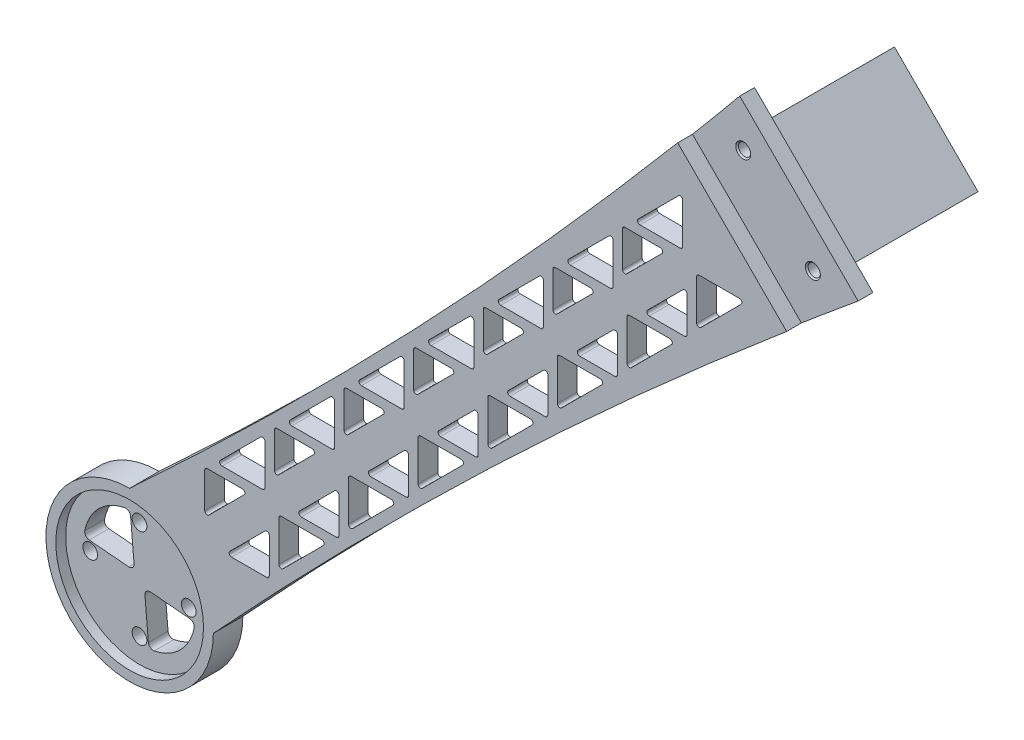
SolidWorks part; units mm, degrees
ref_plane "Front Plane" through (0, 0, 0) normal (0, 0, 1) x (1, 0, 0)
ref_plane "Top Plane" through (0, 0, 0) normal (0, 1, 0) x (1, 0, 0)
ref_plane "Right Plane" through (0, 0, 0) normal (1, 0, 0) x (0, 0, -1)
sketch "Sketch1" plane through (0, 0, 0) normal (0, 0, 1) x (1, 0, 0)
  line L0 (-180.9361, -180.9361) -> (-48, -48) construction
  line L9 (-60.0208, -35.9792) -> (-35.9792, -60.0208)
  arc A0 (-180.9361, -163.9361) -> (-163.9361, -180.9361) centre (-180.9361, -180.9361) ccw
  arc A1 (-180.9361, -163.9361) -> (-60.0208, -35.9792) centre (-1063.1797, 790.8656) ccw
  arc A2 (-163.9361, -180.9361) -> (-35.9792, -60.0208) centre (790.8656, -1063.1797) cw
  point P0 (0, 0)
  point P6 (0, 0)
  point P13 (-48, -48)
  dimension "D5" = 34
  dimension "D6" = 34
  dimension "D7" = 1300
  dimension "D1" = 48
  dimension "D2" = 188
  dimension "D3" = 48
extrude "Boss-Extrude1" add sketch "Sketch1" along normal blind 6
sketch "Sketch2" plane through (0, 0, 0) normal (0, 0, -1) x (-1, 0, 0)
  line L0 (48, -48) -> (192.9569, -192.9569) construction
  line L1 (35.9792, -60.0208) -> (60.0208, -35.9792) construction
  arc A0 (163.9361, -180.9361) -> (180.9361, -163.9361) centre (180.9361, -180.9361) ccw construction
ref_plane "Plane1" through (0, 0, 0) normal (-0.7071, 0.7071, 0) x (-0.7071, -0.7071, 0)
sketch "Sketch3" plane through (0, 0, 0) normal (-0.7071, 0.7071, 0) x (-0.7071, -0.7071, 0)
  line L0 (266.8823, 0) -> (252.3234, -40)
  line L1 (252.3234, -40) -> (240.3234, -40)
  line L2 (240.3234, -40) -> (240.3234, 0)
  line L3 (240.3234, 0) -> (266.8823, 0)
  line L5 (67.8823, 0) -> (272.8823, 0) construction
  dimension "D1" = 40
  dimension "6" = 6
  dimension "D2" = 12
  dimension "D3" = 70
extrude "Boss-Extrude2" add sketch "Sketch3" along normal blind 3 and the other way blind 3
fillet "Fillet1" radius 2 2 edges at (-178.4196, -178.4196, -40) (-169.9343, -169.9343, -40)
sketch "Sketch4" plane through (0, 0, 6) normal (0, 0, 1) x (1, 0, 0)
  line L0 (-60.0208, -35.9792) -> (-35.9792, -60.0208)
  line L1 (-35.9792, -60.0208) -> (-60.0208, -35.9792) construction
  line L2 (-35.9792, -60.0208) -> (-47.4989, -69.628)
  line L3 (-47.4989, -69.628) -> (-69.628, -47.4989)
  line L4 (-69.628, -47.4989) -> (-60.0208, -35.9792)
  arc A0 (-180.9361, -163.9361) -> (-60.0208, -35.9792) centre (-1063.1797, 790.8656) ccw construction
  arc A1 (-35.9792, -60.0208) -> (-163.9361, -180.9361) centre (790.8656, -1063.1797) ccw construction
  dimension "D1" = 15
extrude "Cut-Extrude1" cut sketch "Sketch4" against normal blind 3
sketch "Sketch9" plane through (0, 0, 3) normal (0, 0, 1) x (1, 0, 0)
  line L0 (-48, -48) -> (-56.4853, -56.4853) construction
  line L1 (-48, -48) -> (-192.9569, -192.9569) construction
  line L2 (-59.4701, -45.0152) -> (-45.0152, -59.4701) construction
  line L4 (-35.9792, -60.0208) -> (-60.0208, -35.9792) construction
  point P7 (-52.2426, -52.2426)
  point P10 (-59.3137, -45.1716)
  point P11 (-45.1716, -59.3137)
  point P14 (-52.2426, -52.2426)
  dimension "D1" = 6
  dimension "D2" = 10
  dimension "D3" = 10
sketch "Sketch5" plane through (0, 0, 0) normal (0, 0, -1) x (-1, 0, 0)
  line L0 (48, -48) -> (169.9343, -169.9343) construction
  line L1 (167.813, -172.0557) -> (172.0557, -167.813) construction
  line L2 (41.636, -58.6066) -> (58.6066, -41.636)
  line L3 (41.636, -58.6066) -> (45.8787, -62.8492)
  line L4 (58.6066, -41.636) -> (62.8492, -45.8787)
  line L5 (45.8787, -62.8492) -> (62.8492, -45.8787)
  line L6 (41.636, -58.6066) -> (62.8492, -45.8787) construction
  line L7 (58.6066, -41.636) -> (45.8787, -62.8492) construction
  line L8 (48, -48) -> (192.9569, -192.9569) construction
  line L9 (59.4701, -45.0152) -> (45.0152, -59.4701) construction
  point P6 (52.2426, -52.2426)
  dimension "D1" = 24
  dimension "D2" = 6
extrude "Boss-Extrude3" add sketch "Sketch5" along normal blind 27 contours L2 L3 L5 L4
sketch "Sketch6" plane through (0, 0, 6) normal (0, 0, 1) x (1, 0, 0)
  line L0 (-195.9361, -180.9361) -> (-165.9361, -180.9361) construction
  line L1 (-47.4989, -69.628) -> (-69.628, -47.4989)
  line L2 (-47.4989, -69.628) -> (-69.628, -47.4989)
  line L3 (-180.9361, -195.9361) -> (-180.9361, -165.9361) construction
  circle A0 centre (-180.9361, -180.9361) radius 15
  circle A1 centre (-180.9361, -180.9361) radius 10 construction
  arc A3 (-180.9361, -163.9361) -> (-69.628, -47.4989) centre (-1063.1797, 790.8656) ccw
  arc A4 (-180.9361, -163.9361) -> (-163.9361, -180.9361) centre (-180.9361, -180.9361) ccw
  arc A5 (-47.4989, -69.628) -> (-163.9361, -180.9361) centre (790.8656, -1063.1797) ccw
  arc A6 (-180.9361, -163.9361) -> (-69.628, -47.4989) centre (-1063.1797, 790.8656) ccw
  arc A7 (-180.9361, -163.9361) -> (-163.9361, -180.9361) centre (-180.9361, -180.9361) ccw
  arc A8 (-47.4989, -69.628) -> (-163.9361, -180.9361) centre (790.8656, -1063.1797) ccw
  point P35 (-190.9361, -180.9361)
  point P37 (-170.9361, -180.9361)
  point P39 (-180.9361, -170.9361)
  point P41 (-180.9361, -190.9361)
  dimension "D2" = 30
  dimension "D3" = 20
  dimension "D1" = 0
hole_wizard "Ø3.0mm Dowel Hole2" positions "3DSketch1" profile "Sketch8" hole size "Ø3.0" standard "ISO"
sketch3d "3DSketch1"
  point P0 (-170.9361, -180.9361, 6)
  point P3 (-180.9361, -170.9361, 6)
  point P6 (-190.9361, -180.9361, 6)
  point P9 (-180.9361, -190.9361, 6)
sketch "Sketch8" plane through (-170.9361, -180.9361, 6) normal (1, 0, 0) x (0, -1, 0)
  line L0 (0, 0) -> (0, 5)
  line L1 (0, 5) -> (1.5, 4.0987)
  line L2 (1.5, 4.0987) -> (1.5, 0.025)
  line L3 (1.5, 0.025) -> (1.525, 0)
  line L5 (1.525, 0) -> (0, 0)
  line L6 (-1.5, 0.025) -> (-1.525, 0) construction
  line L10 (0, 5) -> (-1.5, 4.0987) construction
  line L11 (0, -6.35) -> (0, 107.95) construction
  dimension "Hole Dia." = 3
  dimension "Hole Depth" = 5
  dimension "Near C'Sink Dia." = 3.05
  dimension "Near C'Sink Angle" = 90
  dimension "Drill Angle" = 118
extrude "Cut-Extrude4" cut sketch "Sketch6" against normal blind 2 contours A0
hole_wizard "M3 Tapped Hole1" positions "3DSketch2" profile "Sketch10" tap size "M3" standard "IS"
sketch3d "3DSketch2"
  point P0 (-59.3137, -45.1716, 3)
  point P3 (-45.1716, -59.3137, 3)
cosmetic thread "Hole Thread1" parameters "D1"=29.77, "D2"=3
cosmetic thread "Hole Thread2" parameters "D1"=29.77, "D2"=3
sketch "Sketch10" plane through (-59.3137, -45.1716, 3) normal (1, 0, 0) x (0, -1, 0)
  line L0 (0, 0) -> (0, 5)
  line L1 (0, 5) -> (1.25, 4.2489)
  line L2 (1.25, 4.2489) -> (1.25, 0.275)
  line L3 (1.25, 0.275) -> (1.525, 0)
  line L5 (1.525, 0) -> (0, 0)
  line L6 (-1.25, 0.275) -> (-1.525, 0) construction
  line L10 (0, 5) -> (-1.25, 4.2489) construction
  line L11 (0, -6.35) -> (0, 107.95) construction
  dimension "Tap Drill Dia." = 2.5
  dimension "Tap Drill Depth" = 5
  dimension "Near C'Sink Dia." = 3.05
  dimension "Near C'Sink Angle" = 90
  dimension "Drill Angle" = 118
sketch "Sketch11" plane through (0, 0, -27) normal (0, 0, -1) x (-1, 0, 0)
  line L0 (60.7279, -43.7574) -> (43.7574, -60.7279) construction
  line L1 (58.6066, -41.636) -> (62.8492, -45.8787) construction
  line L2 (41.636, -58.6066) -> (45.8787, -62.8492) construction
  point P6 (57.8995, -46.5858)
  point P7 (46.5858, -57.8995)
  point P8 (52.2426, -52.2426)
  dimension "D1" = 8
  dimension "D2" = 8
hole_wizard "M3 Tapped Hole2" positions "Sketch11" profile "Sketch12" tap size "M3" standard "ISO"
cosmetic thread "Hole Thread3" parameters "D1"=6, "D2"=3
cosmetic thread "Hole Thread4" parameters "D1"=6, "D2"=3
sketch "Sketch12" plane through (-46.5858, -57.8995, -27) normal (1, 0, 0) x (0, 1, 0)
  line L0 (0, 0) -> (0, 5)
  line L1 (0, 5) -> (1.25, 4.2489)
  line L2 (1.25, 4.2489) -> (1.25, 0.275)
  line L3 (1.25, 0.275) -> (1.525, 0)
  line L5 (1.525, 0) -> (0, 0)
  line L6 (-1.25, 0.275) -> (-1.525, 0) construction
  line L10 (0, 5) -> (-1.25, 4.2489) construction
  line L11 (0, -6.35) -> (0, 107.95) construction
  dimension "Tap Drill Dia." = 2.5
  dimension "Tap Drill Depth" = 5
  dimension "Near C'Sink Dia." = 3.05
  dimension "Near C'Sink Angle" = 90
  dimension "Drill Angle" = 118
sketch "Sketch13" plane through (0, 0, 4) normal (0, 0, 1) x (1, 0, 0)
  line L0 (-180.9361, -195.9361) -> (-180.9361, -165.9361) construction
  line L1 (-195.9361, -180.9361) -> (-165.9361, -180.9361) construction
  line L2 (-180.9361, -180.9361) -> (-191.5427, -170.3295) construction
  line L3 (-183.1233, -179.8322) -> (-191.1461, -179.1303)
  line L4 (-182.0399, -178.7489) -> (-182.7418, -170.7261)
  line L5 (-180.9361, -180.9361) -> (-177.4291, -177.4291) construction
  line L6 (-48, -48) -> (-192.9569, -192.9569) construction
  line L7 (-178.7489, -182.0399) -> (-170.7261, -182.7418)
  line L8 (-179.8322, -183.1233) -> (-179.1303, -191.1461)
  circle A0 centre (-180.9361, -180.9361) radius 15 construction
  circle A1 centre (-180.9361, -180.9361) radius 15 construction
  arc A2 (-183.9318, -169.8322) -> (-192.0399, -177.9403) centre (-181.9361, -179.9361) ccw
  arc A3 (-182.7418, -170.7261) -> (-183.9318, -169.8322) centre (-183.738, -170.8133) ccw
  arc A4 (-182.0399, -178.7489) -> (-183.1233, -179.8322) centre (-183.0361, -178.836) cw
  arc A5 (-192.0399, -177.9403) -> (-191.1461, -179.1303) centre (-191.0589, -178.1341) ccw
  arc A6 (-178.7489, -182.0399) -> (-179.8322, -183.1233) centre (-178.836, -183.0361) ccw
  arc A7 (-177.9403, -192.0399) -> (-179.1303, -191.1461) centre (-178.1341, -191.0589) cw
  arc A8 (-169.8322, -183.9318) -> (-177.9403, -192.0399) centre (-179.9361, -181.9361) cw
  arc A9 (-170.7261, -182.7418) -> (-169.8322, -183.9318) centre (-170.8133, -183.738) cw
  point P17 (-182.8337, -169.6762)
  dimension "D4" = 1
  dimension "D1" = 45
  dimension "D2" = 10
  dimension "D3" = 2
  dimension "D5" = 40
  dimension "D6" = 40
extrude "Cut-Extrude5" cut sketch "Sketch13" against normal up to surface (4 mm away) up to face at (-52.2426, -52.2426, 0)
sketch "Sketch15" plane through (0, 0, 6) normal (0, 0, 1) x (1, 0, 0)
  line L0 (-58.5634, -58.5634) -> (-170.3295, -170.3295) construction
  line L1 (-69.628, -47.4989) -> (-47.4989, -69.628) construction
  circle A0 centre (-180.9361, -180.9361) radius 15 construction
sketch "Sketch16" plane through (0, 0, 0) normal (0, 0, -1) x (-1, 0, 0)
  line L0 (70.4285, -50.7681) -> (50.7681, -70.4285)
  line L2 (45.8787, -62.8492) -> (62.8492, -45.8787) construction
  line L3 (161.3216, -175.9132) -> (175.9132, -161.3216)
  line L4 (167.813, -172.0557) -> (172.0557, -167.813) construction
  line L8 (59.9145, -38.2069) -> (38.2069, -59.9145)
  arc A11 (59.9145, -38.2069) -> (180.3609, -165.4467) centre (1063.1797, 790.8656) ccw
  arc A12 (165.4467, -180.3609) -> (38.2069, -59.9145) centre (-790.8656, -1063.1797) ccw
  arc A13 (165.4467, -180.3609) -> (180.3609, -165.4467) centre (180.9361, -180.9361) ccw
  arc A14 (70.4285, -50.7681) -> (175.9132, -161.3216) centre (1063.1797, 790.8656) ccw
  arc A15 (161.3216, -175.9132) -> (50.7681, -70.4285) centre (-790.8656, -1063.1797) ccw
  dimension "D1" = 1.5
extrude "Cut-Extrude6" cut sketch "Sketch16" against normal blind 2 contours L3 A14 L0 A15
sketch "Sketch17" plane through (0, 0, 6) normal (0, 0, 1) x (1, 0, 0)
  line L0 (-65.2741, -68.6025) -> (-57.0817, -68.6025)
  line L1 (-73.5522, -60.8243) -> (-60.8243, -73.5522) construction
  line L2 (-50.4509, -69.5044) -> (-69.5044, -50.4509)
  line L3 (-50.4509, -69.5044) -> (-69.5044, -50.4509)
  line L4 (-58.5634, -58.5634) -> (-170.3295, -170.3295) construction
  line L5 (-56.7281, -69.456) -> (-64.9205, -77.6484)
  line L6 (-65.7741, -69.1025) -> (-65.7741, -77.2949)
  arc A0 (-56.7281, -69.456) -> (-57.0817, -68.6025) centre (-57.0817, -69.1025) ccw
  arc A1 (-65.7741, -69.1025) -> (-65.2741, -68.6025) centre (-65.2741, -69.1025) cw
  arc A2 (-64.9205, -77.6484) -> (-65.7741, -77.2949) centre (-65.2741, -77.2949) cw
  arc A6 (-180.1748, -165.9554) -> (-69.5044, -50.4509) centre (-1063.1797, 790.8656) ccw
  arc A7 (-180.1748, -165.9554) -> (-165.9554, -180.1748) centre (-180.9361, -180.9361) ccw
  arc A8 (-50.4509, -69.5044) -> (-165.9554, -180.1748) centre (790.8656, -1063.1797) ccw
  arc A9 (-180.1748, -165.9554) -> (-69.5044, -50.4509) centre (-1063.1797, 790.8656) ccw
  arc A10 (-180.1748, -165.9554) -> (-165.9554, -180.1748) centre (-180.9361, -180.9361) ccw
  arc A11 (-50.4509, -69.5044) -> (-165.9554, -180.1748) centre (790.8656, -1063.1797) ccw
  point P3 (-67.1883, -67.1883)
  point P5 (-65.7741, -68.6025)
  point P8 (-60.8243, -73.5522)
  point P14 (-55.8746, -68.6025)
  point P22 (-65.7741, -68.6025)
  point P25 (-65.7741, -78.502)
  dimension "D5" = 0.5
  dimension "D6" = 0.5
  dimension "D2" = 18
  dimension "D3" = 14
  dimension "D4" = 7
  dimension "D1" = 2
extrude "Cut-Extrude8" cut sketch "Sketch17" against normal blind 9 contours A2 L5 A0 L0 A1 L6
pattern_linear "LPattern1" count 7 spacing 20 along (-0.7071, -0.7071, 0) of "Cut-Extrude8"
mirror "Mirror2" about plane through (0, 0, 0) normal (-0.7071, 0.7071, 0) of "LPattern1"
sketch "Sketch18" plane through (0, 0, 6) normal (0, 0, 1) x (1, 0, 0)
  line L0 (-79.9792, -75.7365) -> (-72.8219, -68.5793)
  line L2 (-80.8327, -75.383) -> (-80.8327, -68.2257)
  line L3 (-80.3327, -67.7257) -> (-73.1755, -67.7257)
  line L4 (-82.7446, -79.4162) -> (-82.7446, -71.2238) construction
  line L5 (-69.1025, -65.7741) -> (-77.2949, -65.7741) construction
  arc A1 (-73.1755, -67.7257) -> (-72.8219, -68.5793) centre (-73.1755, -68.2257) cw
  arc A2 (-80.8327, -75.383) -> (-79.9792, -75.7365) centre (-80.3327, -75.383) ccw
  arc A3 (-80.8327, -68.2257) -> (-80.3327, -67.7257) centre (-80.3327, -68.2257) cw
  dimension "D2" = 0.5
extrude "Cut-Extrude9" cut sketch "Sketch18" against normal blind 39
pattern_linear "LPattern2" count 7 spacing 20 along (-0.7071, -0.7071, 0) of "Cut-Extrude9"
mirror "Mirror3" about plane through (0, 0, 0) normal (-0.7071, 0.7071, 0) of "LPattern2"
sketch "Sketch19" plane through (2.1213, -2.1213, 0) normal (0.7071, -0.7071, 0) x (0, 0, -1)
  line L0 (19, -240.3234) -> (19, -259.751) construction
  line L1 (3, -242.3234) -> (16, -242.3234)
  line L2 (17, -243.3234) -> (17, -257.8662)
  line L3 (16.342, -258.8059) -> (3.342, -263.5375)
  line L4 (2, -262.5978) -> (2, -243.3234)
  line L5 (22, -242.3234) -> (36.6931, -242.3234)
  line L6 (0, -266.8823) -> (38.684, -252.8024)
  line L7 (40, -250.923) -> (40, -242.3234)
  line L8 (38, -240.3234) -> (0, -240.3234)
  line L9 (0, -240.3234) -> (0, -254.5516)
  line L10 (0, -254.5516) -> (0, -257.2129)
  line L11 (0, -257.2129) -> (0, -266.8823)
  line L12 (0, -266.8823) -> (38.684, -252.8024) construction
  line L13 (40, -250.923) -> (40, -242.3234) construction
  line L14 (38, -240.3234) -> (0, -240.3234) construction
  line L15 (0, -240.3234) -> (0, -254.5516) construction
  line L16 (0, -254.5516) -> (0, -257.2129) construction
  line L17 (0, -257.2129) -> (0, -266.8823) construction
  line L18 (37.6931, -243.3234) -> (37.6931, -250.1447)
  line L19 (37.0351, -251.0844) -> (22.342, -256.4323)
  line L20 (21, -255.4926) -> (21, -243.3234)
  arc A0 (17, -257.8662) -> (16.342, -258.8059) centre (16, -257.8662) cw
  arc A1 (3, -242.3234) -> (2, -243.3234) centre (3, -243.3234) ccw
  arc A2 (38.684, -252.8024) -> (40, -250.923) centre (38, -250.923) ccw
  arc A3 (40, -242.3234) -> (38, -240.3234) centre (38, -242.3234) ccw
  arc A4 (38.684, -252.8024) -> (40, -250.923) centre (38, -250.923) ccw construction
  arc A5 (40, -242.3234) -> (38, -240.3234) centre (38, -242.3234) ccw construction
  arc A6 (2, -262.5978) -> (3.342, -263.5375) centre (3, -262.5978) ccw
  arc A7 (17, -243.3234) -> (16, -242.3234) centre (16, -243.3234) ccw
  arc A8 (36.6931, -242.3234) -> (37.6931, -243.3234) centre (36.6931, -243.3234) cw
  arc A9 (37.6931, -250.1447) -> (37.0351, -251.0844) centre (36.6931, -250.1447) cw
  arc A10 (22.342, -256.4323) -> (21, -255.4926) centre (22, -255.4926) cw
  arc A11 (21, -243.3234) -> (22, -242.3234) centre (22, -243.3234) cw
  dimension "D5" = 1
  dimension "D7" = 1
  dimension "D2" = 2
  dimension "D3" = 2
  dimension "D4" = 4
  dimension "D6" = 2
  dimension "D1" = 0
extrude "Cut-Extrude10" cut sketch "Sketch19" against normal blind 9
